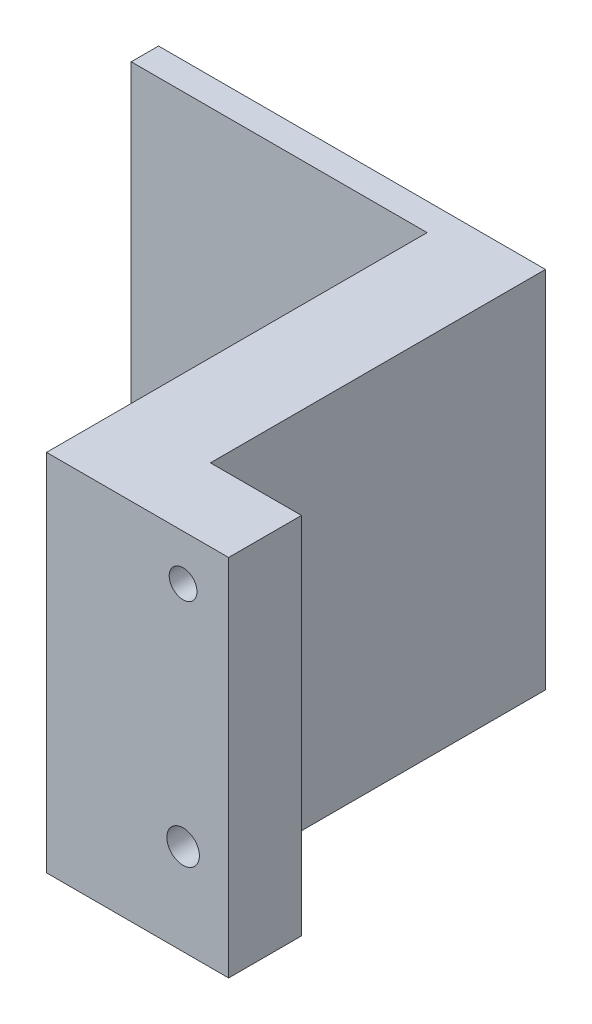
SolidWorks part; units mm, degrees
ref_plane "Front Plane" through (0, 0, 0) normal (0, 0, 1) x (1, 0, 0)
ref_plane "Top Plane" through (0, 0, 0) normal (0, 1, 0) x (1, 0, 0)
ref_plane "Right Plane" through (0, 0, 0) normal (1, 0, 0) x (0, 0, -1)
sketch "Sketch1" plane through (0, 0, 0) normal (0, 0, 1) x (1, 0, 0)
  line L1 (39.9189, 24.9423) -> (59.9189, 24.9423) construction
  line L3 (39.9189, 4.9423) -> (59.9189, 4.9423) construction
  line L4 (59.9189, 24.9423) -> (59.9189, 4.9423) construction
  line L5 (24.9189, 32.4423) -> (44.9189, 32.4423)
  line L6 (24.9189, 32.4423) -> (24.9189, -7.5577)
  line L7 (24.9189, -7.5577) -> (44.9189, -7.5577)
  line L8 (44.9189, 32.4423) -> (44.9189, -7.5577)
  line L9 (24.9189, -7.5577) -> (2.4189, -7.5577)
  line L10 (24.9189, -7.5577) -> (24.9189, 32.4423)
  line L11 (24.9189, 32.4423) -> (2.4189, 32.4423)
  line L12 (2.4189, -7.5577) -> (2.4189, 32.4423)
  line L17 (44.9189, 32.4423) -> (49.9189, 32.4423)
  line L18 (44.9189, 32.4423) -> (44.9189, -7.5577)
  line L19 (44.9189, -7.5577) -> (49.9189, -7.5577)
  line L20 (49.9189, 32.4423) -> (49.9189, -7.5577)
  line L21 (49.9189, 32.4423) -> (54.9189, 32.4423)
  line L22 (49.9189, 32.4423) -> (49.9189, -7.5577)
  line L23 (49.9189, -7.5577) -> (54.9189, -7.5577)
  line L24 (54.9189, 32.4423) -> (54.9189, -7.5577)
  line L25 (44.9189, 32.4423) -> (34.9189, 32.4423)
  line L26 (44.9189, 32.4423) -> (44.9189, -7.5577)
  line L27 (44.9189, -7.5577) -> (34.9189, -7.5577)
  line L28 (34.9189, 32.4423) -> (34.9189, -7.5577)
  line L29 (51.6837, 24.4615) -> (53.3828, 27.4802)
  line L30 (53.3828, 27.4802) -> (51.618, 30.4611)
  line L31 (51.618, 30.4611) -> (48.1541, 30.4232)
  line L32 (48.1541, 30.4232) -> (46.455, 27.4044)
  line L33 (46.455, 27.4044) -> (48.2198, 24.4235)
  line L34 (48.2198, 24.4235) -> (51.6837, 24.4615)
  line L35 (51.6837, 5.4232) -> (48.2198, 5.4611)
  line L36 (48.2198, 5.4611) -> (46.455, 2.4802)
  line L37 (46.455, 2.4802) -> (48.1541, -0.5385)
  line L38 (48.1541, -0.5385) -> (51.618, -0.5765)
  line L39 (51.618, -0.5765) -> (53.3828, 2.4044)
  line L40 (53.3828, 2.4044) -> (51.6837, 5.4232)
  circle A2 centre (13.6689, 7.4423) radius 1.4
  circle A3 centre (13.6689, -2.5577) radius 1.4
  circle A4 centre (49.9189, 27.4423) radius 1.5249
  circle A5 centre (49.9189, 2.4423) radius 1.7864
  circle A6 centre (49.9189, 27.4423) radius 3 construction
  circle A7 centre (49.9189, 2.4423) radius 3 construction
  point P4 (0, 0)
  dimension "D3" = 40
  dimension "D4" = 10
  dimension "D5" = 10
  dimension "D10" = 11.25
  dimension "D11" = 10
  dimension "D12" = 5
  dimension "D13" = 11.25
  dimension "D14" = 2.8
  dimension "D15" = 2.8
  dimension "D16" = 5
  dimension "D17" = 25
  dimension "D18" = 10
  dimension "D2" = 20
  dimension "D9" = 22.5
  dimension "D19" = 5
  dimension "D21" = 6
  dimension "D22" = 6
extrude "Boss-Extrude1" add sketch "Sketch1" along normal blind 5 contours L40 L39 L38 L20 L23 L24 L21 L31 L30 L29 L34 L35 | L38 L37 L36 L35 L20 L34 L33 L32 L31 L17 L8 L19 | A5 L22 L38 L39 L40 L35 | A5 L22 L35 L36 L37 L38 | A4 L22 L34 L29 L30 L31 | A4 L22 L31 L32 L33 L34 | L26 L25 L28 L27 region at (47.206, 11.9806, 0) region at (52.6318, 11.9806, 0) region at (51.4802, 27.4451, 0) region at (48.3576, 27.4396, 0) region at (49.0373, -0.4788, 0) region at (49.9883, 0.049, 0)
extrude "Boss-Extrude2" add sketch "Sketch1<4>" against normal blind 3 contours L38 L37 L36 L35 L20 L34 L33 L32 L31 L17 L8 L19 | L40 L39 L38 L20 L23 L24 L21 L31 L30 L29 L34 L35 | L5 L28 L7 L8 region at (39.9189, 12.4423, 0) region at (47.206, 11.9806, 0) region at (52.6318, 11.9806, 0)
sketch "Sketch1<4>" plane through (0, 0, 0) normal (0, 0, 1) x (1, 0, 0) same geometry as "Sketch1"
extrude "Boss-Extrude3" add sketch "Sketch1<5>" against normal blind 44.8 from surface contours L5 L28 L7 L8 region at (39.9189, 12.4423, 0) starting at face at (51.4438, 27.4423, 5)
sketch "Sketch1<5>" plane through (0, 0, 0) normal (0, 0, 1) x (1, 0, 0) same geometry as "Sketch1"
extrude "Boss-Extrude4" add sketch "Sketch1<6>" along normal blind 3 from surface contours L12 L9 L6 L11 A3 A2 | L28 L5 L6 L7 region at (29.9189, 12.4423, 0) region at (13.6689, 12.581, 0) starting at face at (39.9189, 12.4423, -39.8)
sketch "Sketch1<6>" plane through (0, 0, 0) normal (0, 0, 1) x (1, 0, 0) same geometry as "Sketch1"
